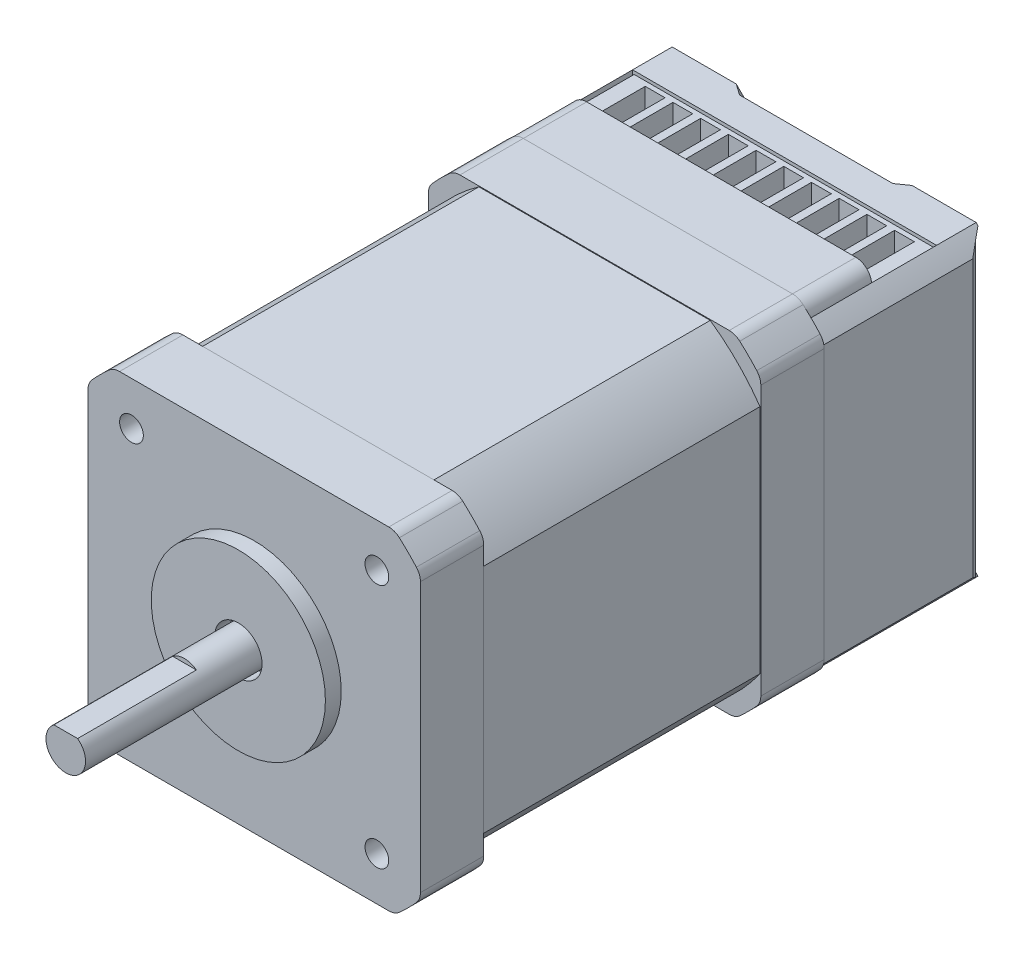
SolidWorks part; units mm, degrees
ref_plane "Ebene vorne" through (0, 0, 0) normal (0, 0, 1) x (1, 0, 0)
ref_plane "Ebene oben" through (0, 0, 0) normal (0, 1, 0) x (1, 0, 0)
ref_plane "Ebene rechts" through (0, 0, 0) normal (1, 0, 0) x (0, 0, -1)
sketch "Skizze1" plane through (0, 0, 0) normal (0, 0, 1) x (1, 0, 0)
  line L1 (-21, -21) -> (21, -21)
  line L2 (-21, -21) -> (-21, 21)
  line L3 (-21, 21) -> (21, 21)
  line L4 (21, -21) -> (21, 21)
  line L5 (-21, -21) -> (21, 21) construction
  line L6 (-21, 21) -> (21, -21) construction
  point P0 (0, 0)
  dimension "D1" = 42
  dimension "D2" = 42
extrude "Aufsatz-Linear austragen1" add sketch "Skizze1" along normal mid plane 51
sketch "Skizze2" plane through (0, 0, 25.5) normal (0, 0, 1) x (1, 0, 0)
  circle A0 centre (0, 0) radius 27.5
  dimension "D1" = 55
sketch "Skizze3" plane through (0, 0, 25.5) normal (0, 0, 1) x (1, 0, 0)
  circle A0 centre (0, 0) radius 11
  circle A1 centre (0, 0) radius 3
  dimension "D1" = 22
  dimension "D2" = 6
extrude "Aufsatz-Linear austragen2" add sketch "Skizze3" along normal blind 2
sketch "Skizze4" plane through (0, 0, 25.5) normal (0, 0, 1) x (1, 0, 0)
  line L1 (-15.5, -15.5) -> (15.5, -15.5)
  line L2 (-15.5, -15.5) -> (-15.5, 15.5)
  line L3 (-15.5, 15.5) -> (15.5, 15.5)
  line L4 (15.5, -15.5) -> (15.5, 15.5)
  line L5 (-15.5, -15.5) -> (15.5, 15.5) construction
  line L6 (-15.5, 15.5) -> (15.5, -15.5) construction
  point P0 (0, 0)
  dimension "D1" = 31
  dimension "D2" = 31
sketch "Skizze5" plane through (0, 0, 25.5) normal (0, 0, 1) x (1, 0, 0)
  circle A0 centre (-15.5, 15.5) radius 1.5
  circle A1 centre (15.5, 15.5) radius 1.5
  circle A2 centre (-15.5, -15.5) radius 1.5
  circle A3 centre (15.5, -15.5) radius 1.5
  dimension "D1" = 3
extrude "Schnitt-Linear austragen2" cut sketch "Skizze5" against normal blind 10
sketch "Skizze6" plane through (0, 0, 27.5) normal (0, 0, 1) x (1, 0, 0)
  circle A0 centre (0, 0) radius 2.5
  dimension "D1" = 5
extrude "Aufsatz-Linear austragen3" add sketch "Skizze6" along normal blind 21.8 and the other way blind 10
sketch "Skizze10" plane through (0, 0, 49.3) normal (0, 0, 1) x (1, 0, 0)
  line L1 (-6.775, 11.5682) -> (7.5774, 11.5682)
  line L2 (-6.775, 11.5682) -> (-6.775, 2)
  line L3 (-6.775, 2) -> (7.5774, 2)
  line L4 (7.5774, 11.5682) -> (7.5774, 2)
  dimension "D1" = 2
extrude "Schnitt-Linear austragen4" cut sketch "Skizze10" against normal blind 15
ref_plane "Ebene1" through (0, 0, 0) normal (1, 0, 0) x (0, 0, -1)
ref_plane "Ebene2" through (0, 0, 0) normal (0, 1, 0) x (1, 0, 0)
extrude "Schnitt-Linear austragen5" cut sketch "Skizze2" against normal through all flip side to cut
sketch "Skizze11" plane through (0, 0, 25.5) normal (0, 0, 1) x (1, 0, 0)
  line L0 (-14.6096, 20.9) -> (14.6096, 20.9)
  line L1 (-20.9, 14.6096) -> (-20.9, -14.6096)
  line L2 (-14.6096, -20.9) -> (14.6096, -20.9)
  line L3 (20.9, -14.6096) -> (20.9, 14.6096)
  line L4 (21, -17.7553) -> (21, 17.7553) construction
  line L5 (17.7553, 21) -> (-17.7553, 21) construction
  line L6 (-21, 17.7553) -> (-21, -17.7553) construction
  line L7 (-17.7553, -21) -> (17.7553, -21) construction
  arc A0 (-20.9, -14.6096) -> (-14.6096, -20.9) centre (0, 0) ccw
  circle A1 centre (0, 0) radius 28.2253
  arc A2 (14.6096, -20.9) -> (20.9, -14.6096) centre (0, 0) ccw
  arc A3 (20.9, 14.6096) -> (14.6096, 20.9) centre (0, 0) ccw
  arc A4 (-14.6096, 20.9) -> (-20.9, 14.6096) centre (0, 0) ccw
  dimension "D1" = 51
  dimension "D2" = 0.1
  dimension "D3" = 0.1
  dimension "D4" = 0.1
  dimension "D5" = 0.1
extrude "Schnitt-Linear austragen6" cut sketch "Skizze11" against normal offset from surface (35 mm away) 8 from offset 8 up to face at (0, 0, -25.5) offset against normal yes
fillet "Verrundung1" radius 2 16 edges at (17.7553, -21, 21.5) (21, -17.7553, 21.5) (21, -17.7553, -21.5) (17.7553, -21, -21.5) (-21, -17.7553, -21.5) (-17.7553, -21, -21.5) (-17.7553, -21, 21.5) (-21, -17.7553, 21.5) (-17.7553, 21, 21.5) (-21, 17.7553, 21.5) (-21, 17.7553, -21.5) (-17.7553, 21, -21.5) (21, 17.7553, -21.5) (17.7553, 21, -21.5) (21, 17.7553, 21.5) (17.7553, 21, 21.5)
sketch "Skizze12" plane through (0, 0, -25.5) normal (0, 0, -1) x (-1, 0, 0)
  line L0 (-17.0074, 21) -> (17.0074, 21) construction
  line L1 (-19, 21) -> (19, 21)
  line L2 (-19, 21) -> (-19, 6)
  line L3 (-19, 6) -> (19, 6)
  line L4 (19, 21) -> (19, 6)
  dimension "D1" = 19
  dimension "D2" = 19
  dimension "D3" = 15
extrude "Aufsatz-Linear austragen4" add sketch "Skizze12" along normal blind 8 separate body
fillet "Verrundung2" radius 2 2 edges at (-19, 21, -29.5) (19, 21, -29.5)
sketch "Skizze13" plane through (0, 0, -33.5) normal (0, 0, -1) x (-1, 0, 0)
  line L1 (-19, 6) -> (19, 6)
  line L2 (-19, 6) -> (-19, 19)
  line L3 (-19, 19) -> (19, 19)
  line L4 (19, 6) -> (19, 19)
  arc A0 (19, 19) -> (17, 21) centre (17, 19) ccw construction
extrude "Aufsatz-Linear austragen5" add sketch "Skizze13" along normal blind 8 separate body
sketch "Skizze15" plane through (0, 19, 0) normal (0, 1, 0) x (1, 0, 0)
  line L0 (-19, 33.5) -> (19, 33.5) construction
  line L1 (0.5, 34.1) -> (3, 34.1)
  line L2 (0.5, 34.1) -> (0.5, 40.9)
  line L3 (0.5, 40.9) -> (3, 40.9)
  line L4 (3, 34.1) -> (3, 40.9)
  line L5 (-19, 41.5) -> (19, 41.5) construction
  dimension "D1" = 2.5
  dimension "D2" = 0.5
  dimension "D3" = 0.6
  dimension "D4" = 0.6
extrude "Schnitt-Linear austragen7" cut sketch "Skizze15" against normal blind 8
pattern_linear "Lineares Muster1" count 5 spacing 3.5 along (1, 0, 0) of "Schnitt-Linear austragen7"
mirror "Spiegeln1" about plane through (0, 0, 0) normal (1, 0, 0) of "Lineares Muster1", "Schnitt-Linear austragen7"
sketch "Skizze16" plane through (0, 0, -25.5) normal (0, 0, -1) x (-1, 0, 0)
  line L0 (-19.2, 19.4075) -> (-19.2, 5.7074)
  line L1 (-19.2, 5.7074) -> (19.2, 5.7074)
  line L2 (19.2, 5.7074) -> (19.2, 19.4075)
  line L3 (-21, 17.4439) -> (-21, -17.4439)
  line L4 (-17.4439, -21) -> (17.4439, -21)
  line L5 (21, -17.4439) -> (21, 17.4439)
  arc A0 (-19.2, 19.4075) -> (-21, 17.4439) centre (0, 0) ccw
  arc A1 (21, 17.4439) -> (19.2, 19.4075) centre (0, 0) ccw
  arc A2 (-21, -17.4439) -> (-17.4439, -21) centre (0, 0) ccw
  arc A3 (17.4439, -21) -> (21, -17.4439) centre (0, 0) ccw
  dimension "D1" = 19.2
  dimension "D3" = 54.6
  dimension "D2" = 19.2
  dimension "D4" = 21
  dimension "D5" = 21
  dimension "D6" = 21
extrude "Aufsatz-Linear austragen6" add sketch "Skizze16" along normal blind 16 separate body
sketch "Skizze17" plane through (0, 0, -41.5) normal (0, 0, -1) x (-1, 0, 0)
  line L0 (-19.2, 19.4075) -> (19.2, 19.4075)
  line L1 (21, 17.4439) -> (21, -17.4439)
  line L2 (-21, -17.4439) -> (-21, 17.4439)
  line L3 (-17.4439, -21) -> (17.4439, -21)
  arc A0 (17.4439, -21) -> (21, -17.4439) centre (0, 0) ccw
  arc A1 (21, 17.4439) -> (19.2, 19.4075) centre (0, 0) ccw
  arc A2 (-21, -17.4439) -> (-17.4439, -21) centre (0, 0) ccw
  arc A3 (-19.2, 19.4075) -> (-21, 17.4439) centre (0, 0) ccw
extrude "Aufsatz-Linear austragen7" add sketch "Skizze17" along normal blind 5
sketch "Skizze18" plane through (0, 0, -46.5) normal (0, 0, -1) x (-1, 0, 0)
  line L0 (0, 2.3344) -> (0, -9.554) construction
  line L1 (0, 22.3327) -> (0, -22.3327) construction
  line L2 (5.2211, 2.3344) -> (5.2211, -9.554)
  line L3 (-5.2211, 2.3344) -> (-5.2211, -9.554)
  line L4 (-9.6893, 19.4075) -> (-2.5, 12.2182)
  line L5 (19.2, 19.4075) -> (-19.2, 19.4075) construction
  line L6 (-2.5, 12.2182) -> (-2.5, 6.9181)
  line L7 (-2.5, -14.9333) -> (-8.5667, -21)
  line L8 (-17.4439, -21) -> (17.4439, -21) construction
  line L9 (2.5, 12.2182) -> (9.6893, 19.4075)
  line L10 (9.6893, 19.4075) -> (-9.6893, 19.4075)
  line L11 (2.5, 12.2182) -> (2.5, 6.9181)
  line L12 (2.5, -14.9333) -> (8.5667, -21)
  line L13 (8.5667, -21) -> (-8.5667, -21)
  line L14 (-2.5, -14.1377) -> (-2.5, -14.9333)
  line L15 (2.5, -14.1377) -> (2.5, -14.9333)
  arc A0 (5.2211, 2.3344) -> (2.5, 6.9181) centre (0, 2.3344) ccw
  arc A1 (-5.2211, -9.554) -> (-2.5, -14.1377) centre (0, -9.554) ccw
  arc A2 (-2.5, 6.9181) -> (-5.2211, 2.3344) centre (0, 2.3344) ccw
  arc A3 (2.5, -14.1377) -> (5.2211, -9.554) centre (0, -9.554) ccw
  point P5 (0, -3.6098)
  dimension "D1" = 2.5
  dimension "D2" = 2.5
  dimension "D3" = 45
  dimension "D4" = 45
extrude "Schnitt-Linear austragen8" cut sketch "Skizze18" against normal blind 1
sketch "Skizze19" plane through (0, 0, -45.5) normal (0, 0, -1) x (-1, 0, 0)
  line L0 (0, 7.979) -> (0, 11.017) construction
  line L1 (0, 22.3327) -> (0, -22.3327) construction
  line L2 (-0.7738, 7.979) -> (-0.7738, 11.017)
  line L3 (0.7738, 7.979) -> (0.7738, 11.017)
  arc A0 (-0.7738, 7.979) -> (0.7738, 7.979) centre (0, 7.979) ccw
  arc A1 (0.7738, 11.017) -> (-0.7738, 11.017) centre (0, 11.017) ccw
  point P5 (0, 9.498)
extrude "Aufsatz-Linear austragen8" add sketch "Skizze19" along normal blind 1
sketch "Skizze20" plane through (0, 0, -46.5) normal (0, 0, -1) x (-1, 0, 0)
  line L1 (-11.6444, 10.6744) -> (-11.6444, -9.9681)
  line L4 (-24.1419, -18.4477) -> (-24.1419, 18.4477)
  line L6 (-20.124, 18.4477) -> (-11.6444, 10.6744)
  line L7 (-20.124, 18.4477) -> (-24.1419, 18.4477)
  line L8 (-20.124, 18.4477) -> (-20.124, -18.4477) construction
  line L9 (-20.124, -18.4477) -> (-11.6444, -9.9681)
  line L10 (-20.124, -18.4477) -> (-24.1419, -18.4477)
  arc A0 (-21, -17.4439) -> (-17.4439, -21) centre (0, 0) ccw construction
  arc A1 (-19.2, 19.4075) -> (-21, 17.4439) centre (0, 0) ccw construction
extrude "Schnitt-Linear austragen9" cut sketch "Skizze20" against normal blind 1
mirror "Spiegeln2" about plane through (0, 0, 0) normal (1, 0, 0) of "Schnitt-Linear austragen9"
chamfer "Fase1" distance 1 angle 45 18 edges at (-15.8842, 14.561, -46.5) (-11.6444, 0.3532, -46.5) (-15.8842, -14.2079, -46.5) (6.0947, 15.8128, -46.5) (2.5, 9.5681, -46.5) (4.4896, 4.9996, -46.5) (5.2211, -3.6098, -46.5) (4.4896, -12.2192, -46.5) (5.5334, -17.9666, -46.5) (-5.5334, -17.9666, -46.5) (-4.4896, -12.2192, -46.5) (-5.2211, -3.6098, -46.5) (-4.4896, 4.9996, -46.5) (-2.5, 9.5681, -46.5) (-6.0947, 15.8128, -46.5) (15.8842, -14.2079, -46.5) (11.6444, 0.3532, -46.5) (15.8842, 14.561, -46.5)
sketch "Skizze21" plane through (0, 19.4075, 0) normal (0, 1, 0) x (1, 0, 0)
  line L0 (19.4347, 46.5) -> (21.4638, 43.6127)
  line L1 (21.4638, 43.6127) -> (21.4638, 46.5)
  line L2 (21.4638, 46.5) -> (19.4347, 46.5)
  line L3 (-19.4347, 46.5) -> (-21.351, 43.7732)
  line L4 (-21.351, 43.7732) -> (-21.351, 46.5)
  line L5 (-21.351, 46.5) -> (-19.4347, 46.5)
extrude "Schnitt-Linear austragen10" cut sketch "Skizze21" against normal through all
sketch "Skizze22" plane through (0, 0, -46.5) normal (0, 0, -1) x (-1, 0, 0)
  circle A0 centre (-15.8184, 4.5763) radius 3
  circle A1 centre (16.1585, -12.0298) radius 3
  dimension "D1" = 6
  dimension "D2" = 6
extrude "Schnitt-Linear austragen11" cut sketch "Skizze22" against normal blind 2
